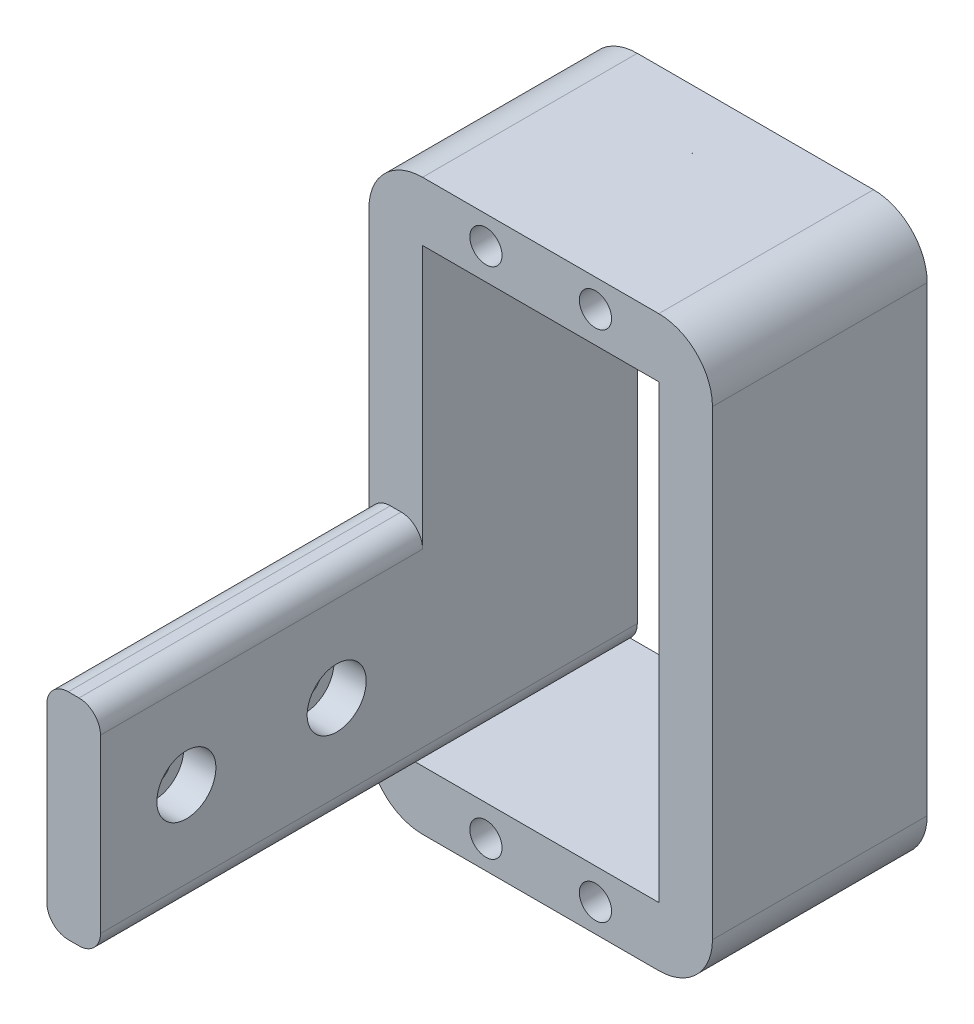
SolidWorks part; units mm, degrees
ref_plane "Front Plane" through (0, 0, 0) normal (0, 0, 1) x (1, 0, 0)
ref_plane "Top Plane" through (0, 0, 0) normal (0, 1, 0) x (1, 0, 0)
ref_plane "Right Plane" through (0, 0, 0) normal (1, 0, 0) x (0, 0, -1)
sketch "Sketch1" plane through (0, 0, 0) normal (0, 0, 1) x (1, 0, 0)
  line L1 (-11, 21) -> (11, 21)
  line L2 (-11, 21) -> (-11, -21)
  line L3 (-11, -21) -> (11, -21)
  line L4 (11, 21) -> (11, -21)
  line L5 (-11, 21) -> (11, -21) construction
  line L6 (-11, -21) -> (11, 21) construction
  line L8 (-16, 26.5) -> (16, 26.5)
  line L9 (-16, 26.5) -> (-16, -26.5)
  line L10 (-16, -26.5) -> (16, -26.5)
  line L11 (16, 26.5) -> (16, -26.5)
  line L12 (-16, 26.5) -> (16, -26.5) construction
  line L13 (-16, -26.5) -> (16, 26.5) construction
  point P0 (0, 0)
  point P6 (0, 0)
  dimension "D1" = 22
  dimension "D2" = 42
  dimension "D4" = 5
  dimension "D3" = 53
extrude "Boss-Extrude1" add sketch "Sketch1" along normal blind 20
sketch "Sketch2" plane through (0, 0, 20) normal (0, 0, 1) x (1, 0, 0)
  line L0 (-16, 26.5) -> (-16, -26.5) construction
  line L1 (-16, -21.5) -> (-11, -21.5)
  line L2 (-16, -21.5) -> (-16, -1.5)
  line L3 (-16, -1.5) -> (-11, -1.5)
  line L4 (-11, -21.5) -> (-11, -1.5)
  line L5 (-11, 21) -> (-11, -21) construction
  line L6 (-16, -26.5) -> (16, -26.5) construction
  dimension "D1" = 20
  dimension "D2" = 5
extrude "Boss-Extrude2" add sketch "Sketch2" along normal blind 30
sketch "Sketch3" plane through (-11, 0, 0) normal (1, 0, 0) x (0, 0, -1)
  line L0 (-50, -21.5) -> (-50, -1.5) construction
  line L1 (-20, -26.5) -> (-20, 26.5) construction
  circle A0 centre (-42, -11.5) radius 2.75
  circle A1 centre (-28, -11.5) radius 2.75
  circle A2 centre (-42, -11.5) radius 1.6
  circle A3 centre (-28, -11.5) radius 1.6
  point P9 (-50, -11.5)
  dimension "D1" = 5.5
  dimension "D4" = 3.2
  dimension "D2" = 8
  dimension "D3" = 8
extrude "Cut-Extrude1" cut sketch "Sketch3" against normal blind 3
extrude "Cut-Extrude2" cut sketch "Sketch3<2>" against normal through all contours A2 | A3 region at (-11, -11.5, 42) region at (-11, -11.5, 28)
sketch "Sketch3<2>" plane through (-11, 0, 0) normal (1, 0, 0) x (0, 0, -1) same geometry as "Sketch3"
sketch "Sketch4" plane through (0, 0, 0) normal (0, 0, -1) x (-1, 0, 0)
  circle A0 centre (-5.1, -23.9) radius 1.5
  circle A1 centre (5.1, -23.9) radius 1.5
  circle A2 centre (-5.1, 23.9) radius 1.5
  circle A3 centre (5.1, 23.9) radius 1.5
  dimension "D1" = 3
extrude "Cut-Extrude3" cut sketch "Sketch4" against normal through all
fillet "Fillet1" radius 5 4 edges at (-16, -26.5, 10) (16, -26.5, 10) (-16, 26.5, 10) (16, 26.5, 10)
fillet "Fillet2" radius 2 4 edges at (-16, -1.5, 35) (-16, -21.5, 35) (-11, -1.5, 35) (-11, -21.5, 35)
